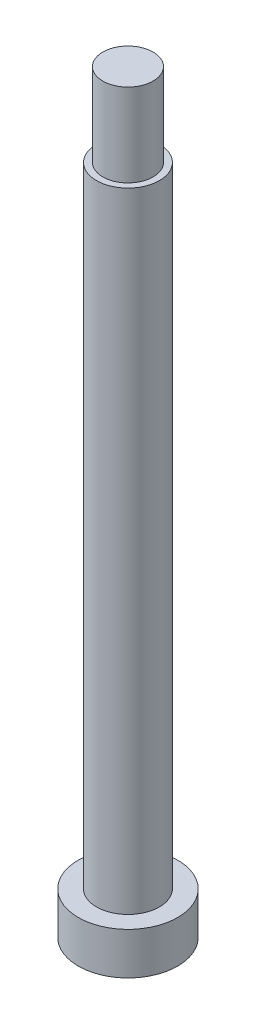
SolidWorks part; units mm, degrees
ref_plane "前视基准面" through (0, 0, 0) normal (0, 0, 1) x (1, 0, 0)
ref_plane "上视基准面" through (0, 0, 0) normal (0, 1, 0) x (1, 0, 0)
ref_plane "右视基准面" through (0, 0, 0) normal (1, 0, 0) x (0, 0, -1)
other "Configuration Table"
sketch "草图1" plane through (0, 0, 0) normal (0, 1, 0) x (1, 0, 0)
  circle A0 centre (0, 0) radius 5
  circle A1 centre (0, 0) radius 7.9
  circle A2 centre (0, 0) radius 4
  dimension "D1" = 8
  dimension "D2" = 10
  dimension "D3" = 15.8
extrude "凸台-拉伸1" add sketch "草图1" along normal blind 119.9 contours A2 region at (0, 0, 0)
extrude "凸台-拉伸2" add sketch "草图1<3>" along normal blind 106.7 contours A0 A2 region at (-4.8586, 0, 0)
sketch "草图1<3>" plane through (0, 0, 0) normal (0, 1, 0) x (1, 0, 0) same geometry as "草图1"
extrude "凸台-拉伸3" add sketch "草图1<4>" along normal blind 6.7 contours A1 A0 region at (-7.6766, 0, 0)
sketch "草图1<4>" plane through (0, 0, 0) normal (0, 1, 0) x (1, 0, 0) same geometry as "草图1"
sketch "草图2" plane through (0, 0, 0) normal (0, -1, 0) x (1, 0, 0)
  line L1 (2.5, 1.4434) -> (0, 2.8868)
  line L2 (0, 2.8868) -> (-2.5, 1.4434)
  line L3 (-2.5, 1.4434) -> (-2.5, -1.4434)
  line L4 (-2.5, -1.4434) -> (0, -2.8868)
  line L5 (0, -2.8868) -> (2.5, -1.4434)
  line L6 (2.5, -1.4434) -> (2.5, 1.4434)
  circle A0 centre (0, 0) radius 2.5 construction
  dimension "D1" = 5
extrude "切除-拉伸1" cut sketch "草图2" against normal blind 3
